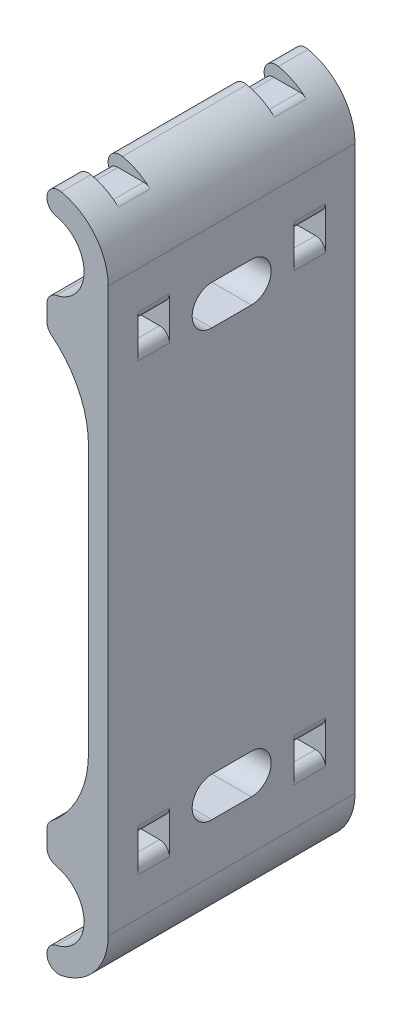
SolidWorks part; units mm, degrees
material "ABS"
ref_plane "Alzado" through (0, 0, 0) normal (0, 0, 1) x (1, 0, 0)
ref_plane "Planta" through (0, 0, 0) normal (0, 1, 0) x (1, 0, 0)
ref_plane "Vista lateral" through (0, 0, 0) normal (1, 0, 0) x (0, 0, -1)
sketch "Croquis1" plane through (0, 0, 0) normal (0, 0, 1) x (1, 0, 0)
  line L5 (-13.465, 0) -> (13.8234, 0) construction
  line L8 (-2, 19.2858) -> (-8.9869, 23.2963)
  line L9 (-2, 19.2858) -> (-2, -19.2858)
  line L10 (0, 28.5) -> (0, -28.5)
  line L11 (-2, -19.2858) -> (-8.9869, -23.2963)
  circle A0 centre (-6, 28.5) radius 3.55
  arc A5 (0, 28.5) -> (-8.9869, 23.2963) centre (-6, 28.5) ccw
  arc A6 (0, -28.5) -> (-8.9869, -23.2963) centre (-6, -28.5) cw
  circle A7 centre (-6, -28.5) radius 3.55
  point P7 (0, 0)
  point P15 (0, 0)
  point P16 (-2, 0)
  point P17 (-2, 0)
  dimension "D1" = 7.1
  dimension "D2" = 57
  dimension "D3" = 2
  dimension "D4" = 6
extrude "Saliente-Extruir1" add sketch "Croquis1" against normal blind 25
fillet "Redondeo1" radius 10 2 edges at (-2, -19.2858, -12.5) (-2, 19.2858, -12.5)
sketch "Croquis2" plane through (0, 0, 0) normal (1, 0, 0) x (0, 0, -1)
  line L0 (-8.2811, 0) -> (45.0775, 0) construction
  line L1 (10.5, 21.5703) -> (14.5, 21.5703) construction
  line L2 (10.5, 23.5703) -> (14.5, 23.5703)
  line L3 (10.5, 19.5703) -> (14.5, 19.5703)
  line L4 (10.5, -21.5703) -> (14.5, -21.5703) construction
  line L5 (10.5, -23.5703) -> (14.5, -23.5703)
  line L6 (10.5, -19.5703) -> (14.5, -19.5703)
  line L7 (0, 13.4955) -> (25, 13.4955) construction
  arc A0 (10.5, 23.5703) -> (10.5, 19.5703) centre (10.5, 21.5703) ccw
  arc A1 (14.5, 19.5703) -> (14.5, 23.5703) centre (14.5, 21.5703) ccw
  arc A2 (10.5, -23.5703) -> (10.5, -19.5703) centre (10.5, -21.5703) cw
  arc A3 (14.5, -19.5703) -> (14.5, -23.5703) centre (14.5, -21.5703) cw
  point P5 (12.5, 21.5703)
  point P12 (12.5, -21.5703)
  point P20 (12.5, 13.4955)
  dimension "D1" = 2
  dimension "D2" = 4
extrude "Cortar-Extruir1" cut sketch "Croquis2" against normal through all
sketch "Croquis3" plane through (0, 0, -25) normal (0, 0, -1) x (-1, 0, 0)
  line L1 (25.3768, -37.4523) -> (6.2082, -37.4523)
  line L2 (25.3768, -37.4523) -> (25.3768, 44.7692)
  line L3 (25.3768, 44.7692) -> (6.2082, 44.7692)
  line L4 (6.2082, -37.4523) -> (6.2082, 44.7692)
extrude "Cortar-Extruir2" cut sketch "Croquis3" against normal through all
sketch "Croquis4" plane through (-2, 0, 0) normal (-1, 0, 0) x (0, 0, 1)
  line L0 (12.0714, 0) -> (-39.4319, 0) construction
  line L1 (-12.5, 40.0029) -> (-12.5, -39.4988) construction
  line L2 (-6.2, 35.4875) -> (-6.2, 33.1875)
  line L3 (-22, 35.4875) -> (-18.8, 35.4875)
  line L4 (-22, 35.4875) -> (-22, 33.1875)
  line L5 (-22, 33.1875) -> (-18.8, 33.1875)
  line L6 (-18.8, 35.4875) -> (-18.8, 33.1875)
  line L7 (-3, 33.1875) -> (-6.2, 33.1875)
  line L8 (-3, 35.4875) -> (-3, 33.1875)
  line L9 (-3, 35.4875) -> (-6.2, 35.4875)
  line L10 (-18.8, -35.4875) -> (-18.8, -33.1875)
  line L11 (-22, -33.1875) -> (-18.8, -33.1875)
  line L12 (-22, -35.4875) -> (-22, -33.1875)
  line L13 (-22, -35.4875) -> (-18.8, -35.4875)
  line L14 (-3, -35.4875) -> (-6.2, -35.4875)
  line L15 (-3, -35.4875) -> (-3, -33.1875)
  line L16 (-3, -33.1875) -> (-6.2, -33.1875)
  line L17 (-6.2, -35.4875) -> (-6.2, -33.1875)
  line L18 (-33.7805, 28.4476) -> (5.9842, 28.4476) construction
  line L19 (-18.8, 21.4078) -> (-18.8, 23.7078)
  line L20 (-22, 23.7078) -> (-18.8, 23.7078)
  line L21 (-22, 21.4078) -> (-22, 23.7078)
  line L22 (-22, 21.4078) -> (-18.8, 21.4078)
  line L23 (-3, 21.4078) -> (-6.2, 21.4078)
  line L24 (-3, 21.4078) -> (-3, 23.7078)
  line L25 (-3, 23.7078) -> (-6.2, 23.7078)
  line L26 (-6.2, 21.4078) -> (-6.2, 23.7078)
  line L27 (4.8883, -28.427) -> (-36.3469, -28.427) construction
  line L28 (-22, -21.3666) -> (-18.8, -21.3666)
  line L29 (-22, -21.3666) -> (-22, -23.6666)
  line L30 (-22, -23.6666) -> (-18.8, -23.6666)
  line L31 (-18.8, -21.3666) -> (-18.8, -23.6666)
  line L32 (-6.2, -21.3666) -> (-6.2, -23.6666)
  line L33 (-3, -23.6666) -> (-6.2, -23.6666)
  line L34 (-3, -21.3666) -> (-3, -23.6666)
  line L35 (-3, -21.3666) -> (-6.2, -21.3666)
  line L36 (0, 13.4955) -> (-25, 13.4955) construction
  line L37 (0, 34.4964) -> (0, 32.0439) construction
  point P43 (-12.5, 13.4955)
  dimension "D1" = 2.3
  dimension "D2" = 3
  dimension "D3" = 3.2
extrude "Cortar-Extruir7" cut sketch "Croquis4" against normal through all both and the other way through all
fillet "Redondeo2" radius 1.2 18 edges at (-6.2082, -34.4964, -23.5) (-6.2082, -34.4964, -1.5) (-6.2082, -32.0439, -12.5) (-6.2082, -24.9561, -12.5) (-6.2082, -21.6476, -23.5) (-6.2082, -21.6476, -17.6493) (-6.2082, -21.6476, -7.3507) (-6.2082, -21.6476, -1.5) (-6.2082, 21.6476, -1.5) (-6.2082, 21.6476, -7.3507) (-6.2082, 21.6476, -23.5) (-6.2082, 21.6476, -17.6493) (-6.2082, 34.4964, -1.5) (-6.2082, 34.4964, -23.5) (-6.2082, 24.9561, -12.5) (-6.2082, 32.0439, -12.5) (-6.2082, -34.4964, -12.5) (-6.2082, 34.4964, -12.5)
fillet "Redondeo3" radius 1 4 edges at (-6.2082, -23.6666, -4.6) (-6.2082, -23.6666, -20.4) (-6.2082, 23.7078, -20.4) (-6.2082, 23.7078, -4.6)
fillet "Redondeo4" radius 1 14 edges at (-6.2082, 33.1875, -4.6) (-6.2082, 33.1875, -20.4) (-6.2082, -33.1875, -4.6) (-6.2082, -33.1875, -20.4) (0, -23.6666, -20.4) (0, -21.3666, -20.4) (0, -21.3666, -4.6) (0, -23.6666, -4.6) (0, 23.7078, -20.4) (0, 21.4078, -20.4) (0, 21.4078, -4.6) (0, 23.7078, -4.6) (-2.2547, 33.1875, -20.4) (-2.2547, 33.1875, -4.6)
